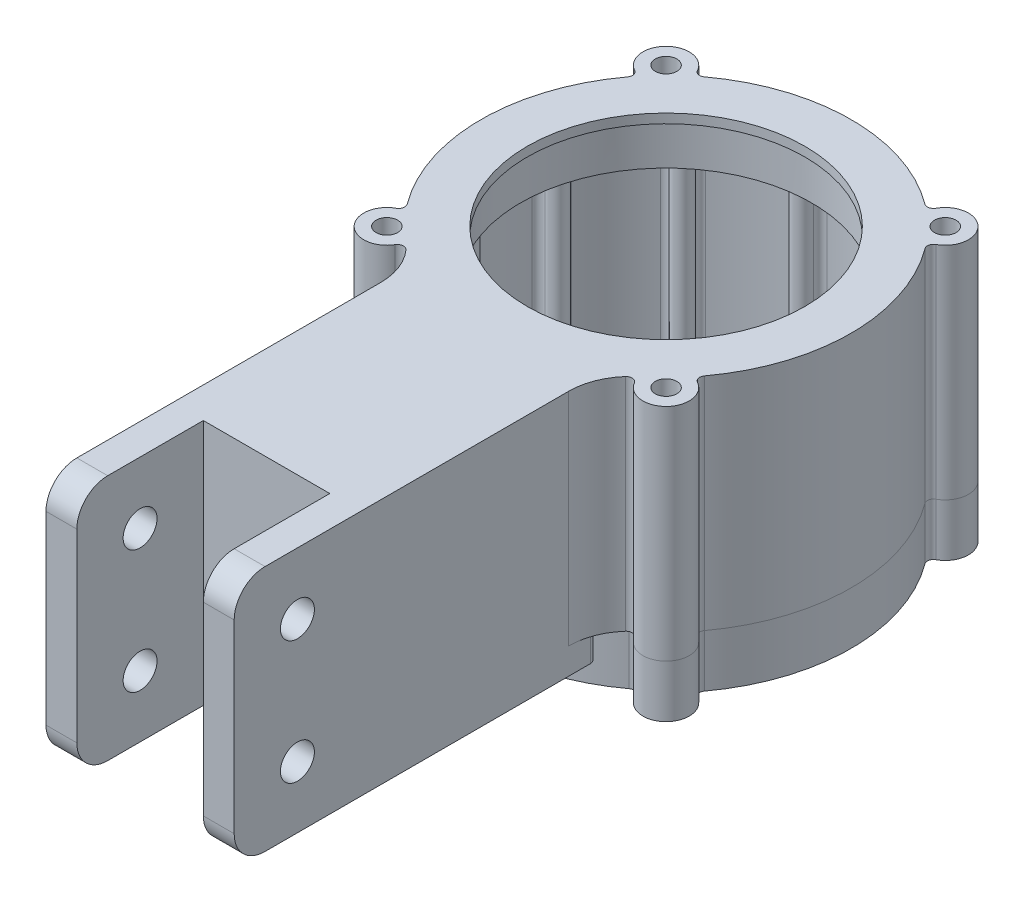
SolidWorks part; units mm, degrees
material "ABS"
ref_plane "Front Plane" through (0, 0, 0) normal (0, 0, 1) x (1, 0, 0)
ref_plane "Top Plane" through (0, 0, 0) normal (0, 1, 0) x (1, 0, 0)
ref_plane "Right Plane" through (0, 0, 0) normal (1, 0, 0) x (0, 0, -1)
ref_axis "Housing Axis" through (0, 24.4803, 0) along (0, -1, 0)
sketch "Sketch1" plane through (0, 0, 0) normal (0, 1, 0) x (1, 0, 0)
  line L0 (0, 0) -> (26.3502, 7.7371) construction
  line L1 (0, 0) -> (26.3502, -7.7371) construction
  line L2 (0, 0) -> (26, 0) construction
  line L3 (26.3502, 7.7371) -> (28.7848, 8.452)
  line L4 (26.3502, -7.7371) -> (28.7848, -8.452)
  circle A0 centre (0, 0) radius 26 construction
  arc A1 (26.2079, 1.4855) -> (26.2079, -1.4855) centre (26, 0) ccw
  arc A2 (26.3502, 7.7371) -> (27.3422, 2.5694) centre (0, 0) cw
  arc A3 (27.3422, -2.5694) -> (26.3502, -7.7371) centre (0, 0) cw
  arc A4 (26.2079, 1.4855) -> (27.3422, 2.5694) centre (26.3466, 2.4759) ccw
  arc A5 (26.2079, -1.4855) -> (27.3422, -2.5694) centre (26.3466, -2.4759) cw
  arc A6 (26.2079, 1.4855) -> (26.2079, -1.4855) centre (0, 0) cw construction
  arc A7 (28.7848, 8.452) -> (28.7848, -8.452) centre (0, 0) cw
  point P14 (27.4605, -0.342)
  dimension "D1" = 52
  dimension "D2" = 3
  dimension "D5" = 1
  dimension "D6" = 30
  dimension "D3" = 32.727
  dimension "D4" = 0.25
extrude "Boss-Extrude1" add sketch "Sketch1" along normal mid plane 27.25
sketch "Sketch2" plane through (0, 13.625, 0) normal (0, 1, 0) x (1, 0, 0)
  circle A0 centre (0, 0) radius 30
  circle A1 centre (0, 0) radius 22.5
  circle A2 centre (0, 0) radius 30 construction
  dimension "D1" = 45
extrude "Boss-Extrude2" add sketch "Sketch2" along normal blind 8.5
pattern_circular "CirPattern1" count 11 over 360 about axis through (0, 24.4803, 0) along (0, -1, 0) of "Boss-Extrude1"
sketch "Sketch3" plane through (0, 22.125, 0) normal (0, -1, 0) x (-1, 0, 0)
  circle A0 centre (0, 0) radius 23.6
  dimension "D1" = 47.2
extrude "Cut-Extrude1" cut sketch "Sketch3" along normal through all from offset 1.5
sketch "Sketch4" plane through (0, 22.125, 0) normal (0, 1, 0) x (1, 0, 0)
  line L0 (-10.25, -85.25) -> (-10.25, -64.75)
  line L1 (-10.25, -64.75) -> (10.25, -64.75)
  line L2 (10.25, -64.75) -> (10.25, -85.25)
  line L3 (10.25, -85.25) -> (-10.25, -64.75) construction
  line L4 (0, -75) -> (0, 0) construction
  line L5 (10.25, -85.25) -> (15.25, -85.25)
  line L6 (15.25, -85.25) -> (15.25, -25.8348)
  line L7 (-10.25, -85.25) -> (-15.25, -85.25)
  line L8 (-15.25, -85.25) -> (-15.25, -25.8348)
  circle A0 centre (0, 0) radius 30 construction
  arc A1 (15.25, -25.8348) -> (-15.25, -25.8348) centre (0, 0) cw
  dimension "D3" = 5
  dimension "D1" = 20.5
  dimension "D2" = 75
extrude "Boss-Extrude3" add sketch "Sketch4" against normal blind 40
fillet "Fillet1" radius 10 2 edges at (15.25, 4.25, 25.8348) (-15.25, 4.25, 25.8348)
fillet "Fillet2" radius 1 2 edges at (-15.25, -15.75, 25.8348) (15.25, -15.75, 25.8348)
sketch "Sketch5" plane through (15.25, 0, 0) normal (1, 0, 0) x (0, 0, -1)
  line L0 (-75, 22.125) -> (-75, 12.125) construction
  line L1 (-85.25, 22.125) -> (-31.0232, 22.125) construction
  line L2 (-75, 12.125) -> (-75, -7.875) construction
  line L3 (-75, -7.875) -> (-75, -17.875) construction
  line L4 (-85.25, -17.875) -> (-27.5307, -17.875) construction
  line L5 (-85.25, 22.125) -> (-64.75, 22.125) construction
  circle A0 centre (-75, 12.125) radius 2.75
  circle A1 centre (-75, -7.875) radius 2.75
  dimension "D2" = 5.5
  dimension "D1" = 20
extrude "Cut-Extrude2" cut sketch "Sketch5" against normal through all both
fillet "Fillet3" radius 5 4 edges at (12.75, -17.875, 85.25) (-12.75, -17.875, 85.25) (12.75, 22.125, 85.25) (-12.75, 22.125, 85.25)
sketch "Sketch6" plane through (0, -13.625, 0) normal (0, -1, 0) x (1, 0, 0)
  line L0 (0, 0) -> (22.6274, 22.6274) construction
  line L1 (0, 0) -> (22.6274, -22.6274) construction
  line L2 (0, 0) -> (-22.6274, -22.6274) construction
  line L3 (0, 0) -> (-22.6274, 22.6274) construction
  line L4 (-22.6274, 22.6274) -> (22.6274, 22.6274) construction
  line L5 (22.6274, 22.6274) -> (22.6274, -22.6274) construction
  line L6 (-15.25, 31.0232) -> (15.25, 31.0232)
  circle A0 centre (22.6274, 22.6274) radius 1.75
  circle A1 centre (22.6274, -22.6274) radius 1.75
  circle A2 centre (-22.6274, -22.6274) radius 1.75
  circle A3 centre (-22.6274, 22.6274) radius 1.75
  arc A4 (24.4256, 19.3366) -> (19.3943, 24.5273) centre (22.6274, 22.6274) ccw
  arc A5 (19.3366, -24.4256) -> (24.4256, -19.3366) centre (22.6274, -22.6274) ccw
  arc A6 (-24.4256, -19.3366) -> (-19.3366, -24.4256) centre (-22.6274, -22.6274) ccw
  arc A7 (-19.3943, 24.5273) -> (-24.4256, 19.3366) centre (-22.6274, 22.6274) ccw
  arc A8 (-18.9375, 23.2674) -> (-15.25, 31.0232) centre (-25.25, 31.0232) ccw construction
  arc A9 (24.1017, 17.8636) -> (24.4256, 19.3366) centre (24.9051, 18.4591) cw
  arc A10 (15.25, 31.0232) -> (18.9375, 23.2674) centre (25.25, 31.0232) ccw construction
  arc A11 (-18.9375, 23.2674) -> (-18.9331, 23.271) centre (-25.25, 31.0232) ccw
  arc A12 (-17.8636, -24.1017) -> (17.8636, -24.1017) centre (0, 0) ccw
  arc A13 (15.25, 31.0232) -> (17.7857, 24.3685) centre (25.25, 31.0232) ccw
  arc A14 (-24.1017, 17.8636) -> (-24.1017, -17.8636) centre (0, 0) ccw
  arc A15 (24.1017, -17.8636) -> (24.1017, 17.8636) centre (0, 0) ccw
  arc A16 (-18.9375, 23.2674) -> (18.9375, 23.2674) centre (0, 0) ccw construction
  arc A17 (24.4256, -19.3366) -> (24.1017, -17.8636) centre (24.9051, -18.4591) cw
  arc A18 (17.8636, -24.1017) -> (19.3366, -24.4256) centre (18.4591, -24.9051) cw
  arc A19 (-19.3366, -24.4256) -> (-17.8636, -24.1017) centre (-18.4591, -24.9051) cw
  arc A20 (-24.4256, -19.3366) -> (-24.1017, -17.8636) centre (-24.9051, -18.4591) ccw
  arc A21 (-24.4256, 19.3366) -> (-24.1017, 17.8636) centre (-24.9051, 18.4591) cw
  arc A22 (-19.3943, 24.5273) -> (-17.7857, 24.3685) centre (-18.5322, 25.034) ccw
  arc A23 (17.7857, 24.3685) -> (19.3943, 24.5273) centre (18.5322, 25.034) ccw
  arc A24 (-17.7857, 24.3685) -> (-15.25, 31.0232) centre (-25.25, 31.0232) ccw
  circle A25 centre (0, 0) radius 27.4626
  arc A26 (9.0211, 25.9387) -> (-1.3479, 27.4295) centre (0, 0) ccw construction
  point P13 (0, 0)
  point P36 (-18.9331, -23.271)
  dimension "D1" = 4
  dimension "D3" = 3.5
  dimension "D4" = 7.5
  dimension "D5" = 1
  dimension "D2" = 32
extrude "Boss-Extrude4" add sketch "Sketch6" against normal up to surface (35.75 mm away) contours A24 A22 A7 A21 A14 A20 A6 A19 A12 A18 A5 A17 A15 A9 A4 A23 A13 L6 A25 A3 A2 A1 A0 region at (0, -13.625, 30.1674) up to face at (0, 22.125, 50.4982)
sketch "Sketch7" plane through (0, -13.625, 0) normal (0, -1, 0) x (1, 0, 0)
  arc A0 (-19.163, 24.0628) -> (-24.4256, 19.3366) centre (-22.6274, 22.6274) ccw
  arc A1 (-24.4256, -19.3366) -> (-19.3366, -24.4256) centre (-22.6274, -22.6274) ccw
  arc A2 (24.4256, 19.3366) -> (19.163, 24.0628) centre (22.6274, 22.6274) ccw
  arc A3 (19.3366, -24.4256) -> (24.4256, -19.3366) centre (22.6274, -22.6274) ccw
  circle A4 centre (-22.6274, 22.6274) radius 1.75 construction
  circle A5 centre (-22.6274, -22.6274) radius 1.75 construction
  circle A6 centre (22.6274, -22.6274) radius 1.75 construction
  circle A7 centre (22.6274, 22.6274) radius 1.75 construction
  circle A8 centre (-22.6274, 22.6274) radius 1.75
  circle A9 centre (-22.6274, -22.6274) radius 1.75
  circle A10 centre (22.6274, -22.6274) radius 1.75
  circle A11 centre (22.6274, 22.6274) radius 1.75
  arc A12 (-19.3943, 24.5273) -> (-24.4256, 19.3366) centre (-22.6274, 22.6274) ccw construction
  arc A13 (-24.4256, -19.3366) -> (-24.1017, -17.8636) centre (-24.9051, -18.4591) ccw construction
  arc A14 (-24.1017, 17.8636) -> (-24.1017, -17.8636) centre (0, 0) ccw construction
  arc A15 (-24.1017, 17.8636) -> (-24.4256, 19.3366) centre (-24.9051, 18.4591) ccw construction
  arc A16 (-24.4256, -19.3366) -> (-24.1017, -17.8636) centre (-24.9051, -18.4591) ccw
  arc A17 (-24.1017, 17.8636) -> (-24.1017, -17.8636) centre (0, 0) ccw
  arc A18 (-24.1017, 17.8636) -> (-24.4256, 19.3366) centre (-24.9051, 18.4591) ccw
  arc A22 (24.1017, -17.8636) -> (24.4256, -19.3366) centre (24.9051, -18.4591) ccw
  arc A23 (24.1017, -17.8636) -> (24.1017, 17.8636) centre (0, 0) ccw
  arc A24 (24.4256, 19.3366) -> (24.1017, 17.8636) centre (24.9051, 18.4591) ccw
  arc A25 (-17.8636, -24.1017) -> (-19.3366, -24.4256) centre (-18.4591, -24.9051) ccw
  arc A26 (-17.8636, -24.1017) -> (17.8636, -24.1017) centre (0, 0) ccw
  arc A27 (19.3366, -24.4256) -> (17.8636, -24.1017) centre (18.4591, -24.9051) ccw
  circle A28 centre (0, 0) radius 23.6
  circle A29 centre (0, 0) radius 23.6 construction
  arc A30 (17.8636, 24.1017) -> (-17.8636, 24.1017) centre (0, 0) ccw [skipped]
  arc A31 (17.8636, 24.1017) -> (19.3366, 24.4256) centre (18.4591, 24.9051) ccw [skipped]
  arc A32 (-19.3366, 24.4256) -> (-17.8636, 24.1017) centre (-18.4591, 24.9051) ccw [skipped]
  arc A33 (17.6411, 23.644) -> (-17.6411, 23.644) centre (0, 0) ccw
  arc A34 (13.7903, 26.6426) -> (-13.7903, 26.6426) centre (0, 0) ccw construction
  arc A35 (17.6411, 23.644) -> (19.163, 24.0628) centre (18.2391, 24.4455) ccw
  arc A36 (-17.6411, 23.644) -> (-19.163, 24.0628) centre (-18.2391, 24.4455) cw
  point P55 (0, 0)
  dimension "D1" = 4
  dimension "D2" = 0.5
extrude "Boss-Extrude5" add sketch "Sketch7" along normal blind 8.5 separate body
sketch "Sketch8" plane through (0, -22.125, 0) normal (0, -1, 0) x (1, 0, 0)
  circle A0 centre (0, 0) radius 22.5
  circle A1 centre (0, 0) radius 22.5 construction
  circle A2 centre (0, 0) radius 23.6 construction
  circle A3 centre (0, 0) radius 23.6
extrude "Boss-Extrude6" add sketch "Sketch8" against normal blind 1.5
sketch "Sketch9" plane through (0, -22.125, 0) normal (0, -1, 0) x (1, 0, 0)
  line L0 (0, 0) -> (-19.8823, 19.8823) construction
  line L1 (-27.291, 12.4736) -> (-12.4736, 27.291) construction
  line L2 (0, 0) -> (0, 29.5) construction
  circle A0 centre (-27.291, 12.4736) radius 2.35
  circle A1 centre (-12.4736, 27.291) radius 2.35
  arc A2 (17.6411, 23.644) -> (-17.6411, 23.644) centre (0, 0) ccw construction
  circle A3 centre (-12.4736, 27.291) radius 5
  circle A4 centre (-27.291, 12.4736) radius 5
  dimension "D1" = 20.955
  dimension "D2" = 4.7
  dimension "D5" = 10
  dimension "D3" = 28.1178
  dimension "D4" = 45
extrude "Boss-Extrude7" add sketch "Sketch9" along normal blind 2.856 and the other way blind 2
sketch "Sketch10" plane through (0, -24.981, 0) normal (0, -1, 0) x (1, 0, 0)
  circle A0 centre (-27.291, 12.4736) radius 2.35 construction
  circle A1 centre (-12.4736, 27.291) radius 2.35 construction
  circle A2 centre (-27.291, 12.4736) radius 2.35
  circle A3 centre (-12.4736, 27.291) radius 2.35
extrude "Cut-Extrude3" cut sketch "Sketch10" against normal blind 4
sketch "Sketch11" plane through (0, -20.125, 0) normal (0, 1, 0) x (1, 0, 0)
  circle A0 centre (-27.291, -12.4736) radius 5 construction
  circle A1 centre (-12.4736, -27.291) radius 5 construction
  circle A2 centre (-27.291, -12.4736) radius 5
  circle A3 centre (-12.4736, -27.291) radius 5
extrude "Boss-Extrude8" add sketch "Sketch11" against normal up to surface (0.856 mm away) up to face at (-26.2194, -20.981, 11.9838)
chamfer "Chamfer1" distance 6 angle 45 2 edges at (-27.2851, -20.125, 12.4709) (-12.263, -20.125, 26.8304)
sketch "Sketch12" plane through (0, -17.875, 0) normal (0, -1, 0) x (1, 0, 0)
  circle A0 centre (-12.4736, 27.291) radius 5.5
  circle A1 centre (-12.4736, 27.291) radius 5 construction
  dimension "D1" = 0.5
extrude "Cut-Extrude4" cut sketch "Sketch12" against normal up to vertex (3.75 mm away) up to point (-16.5617, -14.125, 24.4123)
sketch "Sketch13" plane through (0, -22.125, 0) normal (0, -1, 0) x (1, 0, 0)
  line L0 (-24.8256, 16.8431) -> (-30.3322, 20.579)
  line L1 (-30.3322, 20.579) -> (-20.2983, 29.9184)
  line L2 (-20.2983, 29.9184) -> (-16.5624, 24.4119)
  line L3 (-16.5624, 24.4119) -> (0, 0) construction
  line L4 (0, 0) -> (-24.8256, 16.8431) construction
  arc A0 (-22.7879, 18.8809) -> (-18.8942, 22.273) centre (-22.6274, 22.6274) ccw
  arc A1 (-22.7879, 18.8809) -> (-23.618, 18.4984) centre (-22.8307, 17.8818) ccw
  arc A2 (-24.1017, 17.8636) -> (-24.8352, 16.8289) centre (0, 0) ccw construction
  arc A3 (-18.5267, 22.9567) -> (-18.8942, 22.273) centre (-17.8987, 22.1785) ccw
  arc A4 (-16.5617, 24.4123) -> (-17.6411, 23.644) centre (0, 0) ccw construction
  arc A5 (-19.163, 24.0628) -> (-17.6411, 23.644) centre (-18.2391, 24.4455) ccw construction
  arc A6 (-24.8256, 16.8431) -> (-23.618, 18.4984) centre (0, 0) cw
  arc A8 (-16.5624, 24.4119) -> (-18.5267, 22.9567) centre (0, 0) ccw
  arc A10 (-16.5617, 24.4123) -> (-7.6216, 28.4985) centre (-12.4736, 27.291) ccw construction
  circle A11 centre (-27.291, 12.4736) radius 5 construction
  arc A12 (-19.163, 24.0628) -> (-24.4256, 19.3366) centre (-22.6274, 22.6274) ccw construction
  arc A13 (17.6411, 23.644) -> (-7.6216, 28.4985) centre (0, 0) ccw construction
  arc A14 (-28.9773, 7.7665) -> (-24.1017, -17.8636) centre (0, 0) ccw construction
extrude "Cut-Extrude5" cut sketch "Sketch13" against normal blind 3
equation "\"RotorRadius\"= 26mm"
equation "\"Eccentricity\"= 1.00mm"
equation "\"RollerRadius\"= 1.5mm"
equation "\"GearRatio\"= 10"
equation "\"RollerCount\"=\"GearRatio\" + 1"
equation "\"RotorThickness\"= 6mm"
equation "\"OutputRollerRadius\"= 1.5mm"
equation "\"OutputRollerCount\"= 6"
equation "\"OutputRollerHoleCircleRadius\"=\"RotorRadius\"- 4 * \"OutputRollerRadius\""
equation "\"RotorGap\"= 0.5mm"
equation "\"D1@Sketch1\"=\"RotorRadius\"*2"
equation "\"D2@Sketch1\"=2*\"RollerRadius\""
equation "\"rotorCount\"= 2"
equation "\"D1@Boss-Extrude1\"=(\"rotorCount\" + 2) * \"RotorThickness\" + 0.5mm * (\"rotorCount\" + 4.5)"
equation "\"D1@CirPattern1\"=\"GearRatio\" + 1"
equation "\"D3@Sketch1\"=360deg/(\"GearRatio\" + 1)"
